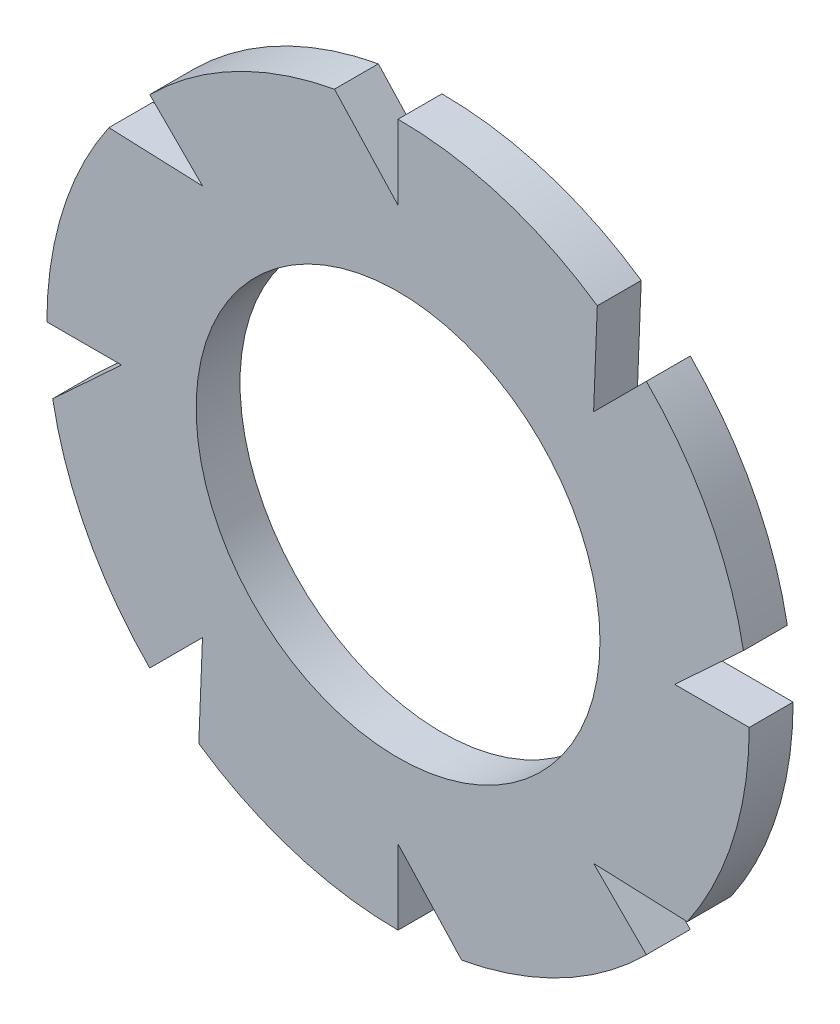
SolidWorks part; units mm, degrees
ref_plane "Front" through (0, 0, 0) normal (0, 0, 1) x (1, 0, 0)
ref_plane "Top" through (0, 0, 0) normal (0, 1, 0) x (1, 0, 0)
ref_plane "Right" through (0, 0, 0) normal (1, 0, 0) x (0, 0, -1)
sketch "Sketch1" plane through (0, 0, 0) normal (0, 0, 1) x (1, 0, 0)
  circle A0 centre (0, 0) radius 4
  circle A1 centre (0, 0) radius 2.3
extrude "Base-Extrude" add sketch "Sketch1" against normal blind 0.5
sketch "Sketch2" plane through (-0.667, 2.3716, 0) normal (0, 0, 1) x (1, 0, 0)
  line L0 (0.667, 1.6284) -> (0.667, 0.7784)
  line L1 (0.667, 0.7784) -> (-0.1184, 1.6284)
  line L2 (-0.1184, 1.6284) -> (0.667, 1.6284)
  line L3 (0.667, -2.3716) -> (8.667, -2.3716) construction
  circle A0 centre (0.667, -2.3716) radius 3.15 construction
  circle A1 centre (0.667, -2.3716) radius 2.3 construction
  circle A3 centre (0.667, -2.3716) radius 4 construction
  dimension "D1" = 6.3
  dimension "D2" = 0.7854
  dimension "D3" = 8
extrude "TypeASlot" cut sketch "Sketch2" against normal through all
pattern_circular "TypeAPattern" count 8 over 360 about axis through (0, 0, -0.5) along (0, 0, 1) of "TypeASlot"
equation "\"D1@Sketch2\" = (  \"D0@Sketch1\" + \"d@Sketch1\" )  / 2"
equation "\"D2@Sketch2\" = \"D0@Sketch1\" * 3.14159 / \"D3@Sketch2\" / 4"
